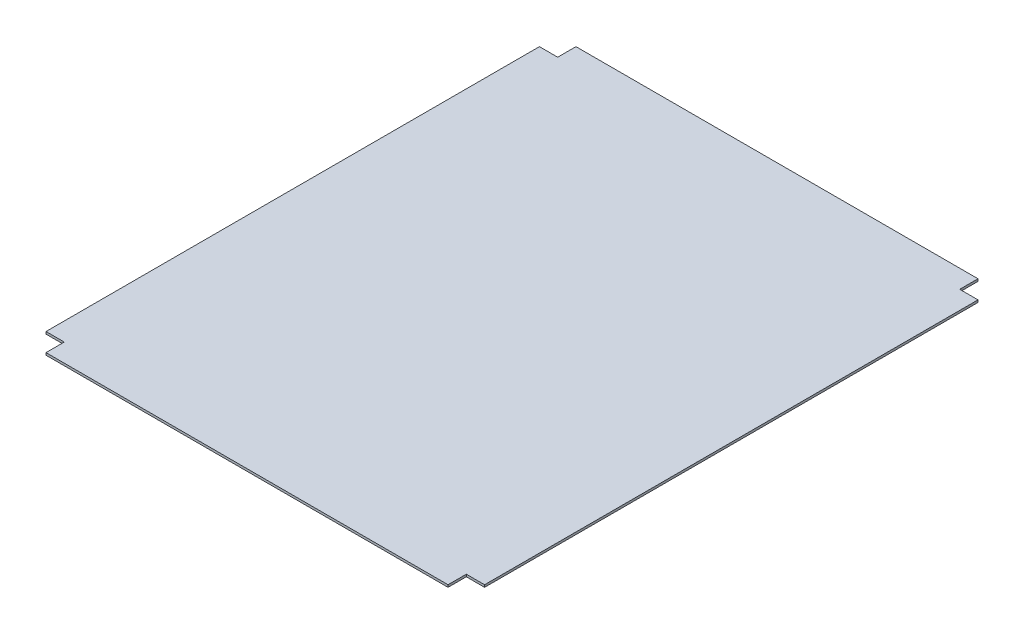
SolidWorks part; units mm, degrees
ref_plane "Front Plane" through (0, 0, 0) normal (0, 0, 1) x (1, 0, 0)
ref_plane "Top Plane" through (0, 0, 0) normal (0, 1, 0) x (1, 0, 0)
ref_plane "Right Plane" through (0, 0, 0) normal (1, 0, 0) x (0, 0, -1)
sketch "Sketch1" plane through (0, 0, 0) normal (0, 1, 0) x (1, 0, 0)
  line L1 (-609.6, -736.6) -> (609.6, -736.6)
  line L2 (-609.6, -736.6) -> (-609.6, 736.6)
  line L3 (-609.6, 736.6) -> (609.6, 736.6)
  line L4 (609.6, -736.6) -> (609.6, 736.6)
  line L5 (-609.6, -736.6) -> (609.6, 736.6) construction
  line L6 (-609.6, 736.6) -> (609.6, -736.6) construction
  point P0 (0, 0)
  dimension "D1" = 1219.2
  dimension "D2" = 1473.2
extrude "Boss-Extrude1" add sketch "Sketch1" along normal mid plane 6.35
sketch "Sketch2" plane through (0, 3.175, 0) normal (0, 1, 0) x (1, 0, 0)
  line L0 (0, 736.6) -> (0, -736.6) construction
  line L1 (-609.6, 736.6) -> (-558.8, 736.6)
  line L2 (-609.6, 736.6) -> (-609.6, 685.8)
  line L3 (-609.6, 685.8) -> (-558.8, 685.8)
  line L4 (-558.8, 736.6) -> (-558.8, 685.8)
  line L5 (609.6, 736.6) -> (-609.6, 736.6) construction
  line L6 (-609.6, -736.6) -> (609.6, -736.6) construction
  line L7 (609.6, 0) -> (-609.6, 0) construction
  line L8 (609.6, -736.6) -> (609.6, 736.6) construction
  line L9 (-609.6, 736.6) -> (-609.6, -736.6) construction
  line L10 (558.8, 736.6) -> (558.8, 685.8)
  line L11 (609.6, 685.8) -> (558.8, 685.8)
  line L12 (609.6, 736.6) -> (609.6, 685.8)
  line L13 (609.6, 736.6) -> (558.8, 736.6)
  line L14 (609.6, -736.6) -> (558.8, -736.6)
  line L15 (609.6, -736.6) -> (609.6, -685.8)
  line L16 (609.6, -685.8) -> (558.8, -685.8)
  line L17 (558.8, -736.6) -> (558.8, -685.8)
  line L18 (-558.8, -736.6) -> (-558.8, -685.8)
  line L19 (-609.6, -685.8) -> (-558.8, -685.8)
  line L20 (-609.6, -736.6) -> (-609.6, -685.8)
  line L21 (-609.6, -736.6) -> (-558.8, -736.6)
  dimension "D1" = 50.8
extrude "Cut-Extrude1" cut sketch "Sketch2" against normal through all
equation "\"width\"= 48in"
equation "\"length\"= 58in"
equation "\"D2@Sketch1\"=\"length\""
equation "\"D1@Sketch1\"=\"width\""
equation "\"square tubing width\"= 2in"
equation "\"D1@Sketch2\"=\"square tubing width\""
